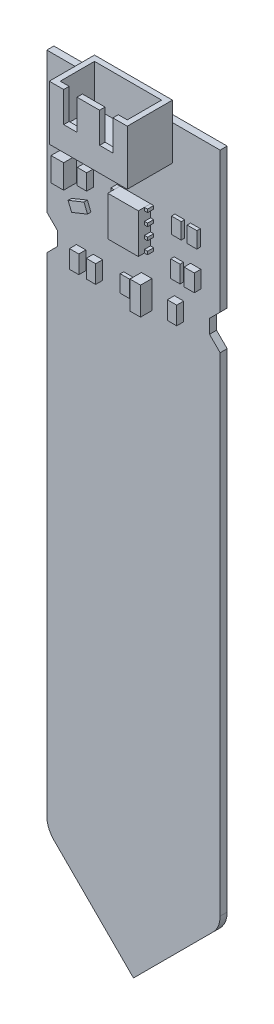
SolidWorks part; units mm, degrees
other "Camera1"
material "Plain Carbon Steel"
ref_plane "Front" through (0, 0, 0) normal (0, 0, 1) x (1, 0, 0)
ref_plane "Top" through (0, 0, 0) normal (0, 1, 0) x (1, 0, 0)
ref_plane "Right" through (0, 0, 0) normal (1, 0, 0) x (0, 0, -1)
ref_axis "X-Axis" through (0, 0, 0) along (1, 0, 0)
ref_axis "Y-Axis" through (0, 0, 0) along (0, 1, 0)
ref_axis "Z-Axis" through (0, 0, 0) along (0, 0, 1)
sketch "Sketch1" plane through (0, 0, 0) normal (0, 0, 1) x (1, 0, 0)
  line L0 (-11.1125, 0) -> (11.1125, 0)
  line L1 (11.1125, 0) -> (11.1125, -18)
  line L2 (-11.1125, 0) -> (-11.1125, -18)
  line L3 (-11.1125, -18) -> (-9.75, -19.3625)
  line L4 (-9.75, -19.3625) -> (-9.75, -21.1375)
  line L5 (-9.75, -21.1375) -> (-11.1125, -22.5)
  line L6 (-11.1125, -22.5) -> (-11.1125, -85.0724)
  line L7 (-10.1826, -87.3174) -> (0, -97.5)
  line L8 (0, -97.5) -> (10.1826, -87.3174)
  line L9 (11.1125, -85.0724) -> (11.1125, -22.5)
  line L10 (11.1125, -22.5) -> (9.75, -21.1375)
  line L11 (9.75, -21.1375) -> (9.75, -19.3625)
  line L12 (9.75, -19.3625) -> (11.1125, -18)
  line L13 (0, 0) -> (0, -97.5) construction
  arc A0 (10.1826, -87.3174) -> (11.1125, -85.0724) centre (7.9375, -85.0724) ccw
  arc A1 (-11.1125, -85.0724) -> (-10.1826, -87.3174) centre (-7.9375, -85.0724) ccw
  point P19 (0, 0)
  point P20 (11.1125, -16.1419)
  point P21 (0, 0)
  dimension "D2" = 3.175
  dimension "D1" = 22.225
  dimension "D3" = 19.5
  dimension "D4" = 18
  dimension "D5" = 4.5
  dimension "D6" = 97.5
extrude "Boss-Extrude1" add sketch "Sketch1" along normal blind 0.9
sketch "Sketch2" plane through (0, 0, 0.9) normal (0, 0, 1) x (1, 0, 0)
  line L0 (11.1125, 0) -> (-11.1125, 0) construction
  line L1 (-7.3125, -22) -> (-6.1125, -22)
  line L2 (-7.3125, -22) -> (-7.3125, -19.7)
  line L3 (-7.3125, -19.7) -> (-6.1125, -19.7)
  line L4 (-6.1125, -22) -> (-6.1125, -19.7)
  line L5 (-5.1525, -22) -> (-3.9525, -22)
  line L6 (-5.1525, -22) -> (-5.1525, -19.7)
  line L7 (-5.1525, -19.7) -> (-3.9525, -19.7)
  line L8 (-3.9525, -22) -> (-3.9525, -19.7)
  line L9 (-11.1125, 0) -> (-11.1125, -18) construction
  line L10 (11.1125, -18) -> (11.1125, 0) construction
  line L11 (-1.2675, -21.86) -> (-0.0675, -21.86)
  line L12 (-1.2675, -21.86) -> (-1.2675, -19.7)
  line L13 (-1.2675, -19.7) -> (-0.0675, -19.7)
  line L14 (-0.0675, -21.86) -> (-0.0675, -19.7)
  line L15 (1.0125, -22.2) -> (2.3625, -22.2)
  line L16 (1.0125, -22.2) -> (1.0125, -18.64)
  line L17 (1.0125, -18.64) -> (2.3625, -18.64)
  line L18 (2.3625, -22.2) -> (2.3625, -18.64)
  line L19 (5.2425, -21.4) -> (6.4425, -21.4)
  line L20 (5.2425, -21.4) -> (5.2425, -19.1)
  line L21 (5.2425, -19.1) -> (6.4425, -19.1)
  line L22 (6.4425, -21.4) -> (6.4425, -19.1)
  line L23 (-7.4957, -16) -> (-5.4576, -15.1717)
  line L24 (-8.9225, -9.79) -> (-7.3125, -9.79)
  line L25 (-8.9225, -9.79) -> (-8.9225, -12.84)
  line L26 (-8.9225, -12.84) -> (-7.3125, -12.84)
  line L27 (-7.3125, -9.79) -> (-7.3125, -12.84)
  line L28 (-6.3125, -10.18) -> (-5.1125, -10.18)
  line L29 (-6.3125, -10.18) -> (-6.3125, -12.22)
  line L30 (-6.3125, -12.22) -> (-5.1125, -12.22)
  line L31 (-5.1125, -10.18) -> (-5.1125, -12.22)
  line L32 (-1.7225, -10.42) -> (2.1875, -10.42)
  line L33 (-1.7225, -10.42) -> (-1.7225, -15.5)
  line L34 (-1.7225, -15.5) -> (2.1875, -15.5)
  line L35 (2.1875, -10.42) -> (2.1875, -15.5)
  line L36 (5.3125, -10) -> (6.5625, -10)
  line L37 (5.3125, -10) -> (5.3125, -12.05)
  line L38 (5.3125, -12.05) -> (6.5625, -12.05)
  line L39 (6.5625, -10) -> (6.5625, -12.05)
  line L40 (7.3125, -10) -> (8.5625, -10)
  line L41 (7.3125, -10) -> (7.3125, -12.05)
  line L42 (7.3125, -12.05) -> (8.5625, -12.05)
  line L43 (8.5625, -10) -> (8.5625, -12.05)
  line L44 (5.2125, -14.8) -> (6.4125, -14.8)
  line L45 (5.2125, -14.8) -> (5.2125, -17)
  line L46 (5.2125, -17) -> (6.4125, -17)
  line L47 (6.4125, -14.8) -> (6.4125, -17)
  line L48 (7.3125, -14.47) -> (8.6325, -14.47)
  line L49 (7.3125, -14.47) -> (7.3125, -16.67)
  line L50 (7.3125, -16.67) -> (8.6325, -16.67)
  line L51 (8.6325, -14.47) -> (8.6325, -16.67)
  line L52 (-7.4957, -16) -> (-7.9475, -14.8883)
  line L53 (-5.4576, -15.1717) -> (-5.9094, -14.06)
  line L54 (-7.9475, -14.8883) -> (-5.9094, -14.06)
  dimension "D1" = 22
  dimension "D2" = 1.2
  dimension "D3" = 2.3
  dimension "D4" = 5
  dimension "D5" = 2.16
  dimension "D6" = 2.16
  dimension "D7" = 1.2
  dimension "D8" = 1.35
  dimension "D9" = 3.56
  dimension "D10" = 0.2
  dimension "D11" = 10.1
  dimension "D12" = 12.38
  dimension "D13" = 5.87
  dimension "D14" = 21.4
  dimension "D15" = 1.61
  dimension "D16" = 3.05
  dimension "D17" = 2.04
  dimension "D18" = 1.2
  dimension "D19" = 5.08
  dimension "D20" = 3.91
  dimension "D21" = 1.32
  dimension "D22" = 1.25
  dimension "D23" = 1.2
  dimension "D24" = 1.25
  dimension "D25" = 2.05
  dimension "D26" = 12.05
  dimension "D27" = 3.8
  dimension "D28" = 5.8
  dimension "D29" = 2.2
  dimension "D30" = 17
  dimension "D31" = 5.9
  dimension "D32" = 3.8
  dimension "D33" = 16.67
  dimension "D34" = 13.3
  dimension "D35" = 15.5
  dimension "D36" = 12.84
  dimension "D37" = 3.8
  dimension "D38" = 12.22
  dimension "D39" = 6
  dimension "D40" = 2.2
  dimension "D41" = 1.2
  dimension "D42" = 16
  dimension "D43" = 14.06
  dimension "D44" = 19.06
extrude "Boss-Extrude2" add sketch "Sketch2" along normal blind 1.57 separate body contours L32 L35 L34 L33
extrude "Boss-Extrude3" add sketch "Sketch2<3>" along normal blind 0.44 separate body contours L43 L40 L41 L42 | L39 L36 L37 L38 | L47 L44 L45 L46 | L54 L52 L23 L53 | L11 L14 L13 L12 region at (-0.6675, -20.78, 0.9) region at (-6.7025, -15.03, 0.9) region at (5.9375, -11.025, 0.9) region at (7.9375, -11.025, 0.9) region at (5.8125, -15.9, 0.9)
sketch "Sketch2<3>" plane through (0, 0, 0.9) normal (0, 0, 1) x (1, 0, 0) same geometry as "Sketch2"
extrude "Boss-Extrude4" add sketch "Sketch2<4>" along normal blind 1.65 separate body contours L27 L24 L25 L26 region at (-8.1175, -11.315, 0.9)
sketch "Sketch2<4>" plane through (0, 0, 0.9) normal (0, 0, 1) x (1, 0, 0) same geometry as "Sketch2"
extrude "Boss-Extrude5" add sketch "Sketch2<5>" along normal blind 0.9 separate body contours L1 L4 L3 L2 | L5 L8 L7 L6 | L31 L28 L29 L30 | L19 L22 L21 L20 region at (-6.7125, -20.85, 0.9) region at (-4.5525, -20.85, 0.9) region at (5.8425, -20.25, 0.9) region at (-5.7125, -11.2, 0.9)
sketch "Sketch2<5>" plane through (0, 0, 0.9) normal (0, 0, 1) x (1, 0, 0) same geometry as "Sketch2"
extrude "Boss-Extrude6" add sketch "Sketch2<6>" along normal blind 1.46 separate body contours L15 L18 L17 L16 region at (1.6875, -20.42, 0.9)
sketch "Sketch2<6>" plane through (0, 0, 0.9) normal (0, 0, 1) x (1, 0, 0) same geometry as "Sketch2"
extrude "Boss-Extrude7" add sketch "Sketch2<7>" along normal blind 0.83 separate body contours L51 L48 L49 L50 region at (7.9725, -15.57, 0.9)
sketch "Sketch2<7>" plane through (0, 0, 0.9) normal (0, 0, 1) x (1, 0, 0) same geometry as "Sketch2"
sketch "Sketch4" plane through (0, 0, 0.9) normal (0, 0, 1) x (1, 0, 0)
  line L0 (11.1125, 0) -> (-11.1125, 0) construction
  line L1 (-5, -4.5) -> (5, -4.5)
  line L2 (-5, -4.5) -> (-5, 2.5)
  line L3 (-5, 2.5) -> (5, 2.5)
  line L4 (5, -4.5) -> (5, 2.5)
  line L5 (0, 0) -> (0, 2.5) construction
  dimension "D1" = 10
  dimension "D2" = 7
  dimension "D3" = 2.5
extrude "Boss-Extrude8" add sketch "Sketch4" along normal blind 5.8 separate body
shell "Shell1" thickness 0.7 removed face at (0, 2.5, 3.8)
sketch "Sketch5" plane through (0, 0, 6.7) normal (0, 0, 1) x (1, 0, 0)
  line L0 (5, 2.5) -> (-5, 2.5) construction
  line L1 (-3.15, 2.5) -> (-1.45, 2.5)
  line L2 (-3.15, 2.5) -> (-3.15, -1.4)
  line L3 (-3.15, -1.4) -> (-1.45, -1.4)
  line L4 (-1.45, 2.5) -> (-1.45, -1.4)
  line L5 (-1.45, -1.4) -> (1.45, -1.4) construction
  line L6 (1.45, 2.5) -> (3.15, 2.5)
  line L7 (1.45, 2.5) -> (1.45, -1.4)
  line L8 (1.45, -1.4) -> (3.15, -1.4)
  line L9 (3.15, 2.5) -> (3.15, -1.4)
  line L10 (0, 0) -> (0, -1.4) construction
  line L11 (5, -4.5) -> (5, 2.5) construction
  dimension "D1" = 2.9
  dimension "D2" = 1.85
  dimension "D3" = 3.9
extrude "Cut-Extrude1" cut sketch "Sketch5" against normal up to next (0.7 mm away)
sketch "Sketch6" plane through (0, 0, 0) normal (0, 0, -1) x (-1, 0, 0)
  line L0 (-2.19, -4.5) -> (-0.35, -4.5) construction
  line L1 (-2.89, -4.15) -> (-2.19, -4.15)
  line L2 (-2.89, -4.15) -> (-2.89, -4.85)
  line L3 (-2.89, -4.85) -> (-2.19, -4.85)
  line L4 (-2.19, -4.15) -> (-2.19, -4.85)
  line L5 (-0.35, -4.15) -> (0.35, -4.15)
  line L6 (-0.35, -4.15) -> (-0.35, -4.85)
  line L7 (-0.35, -4.85) -> (0.35, -4.85)
  line L8 (0.35, -4.15) -> (0.35, -4.85)
  line L9 (2.19, -4.15) -> (2.89, -4.15)
  line L10 (2.19, -4.15) -> (2.19, -4.85)
  line L11 (2.19, -4.85) -> (2.89, -4.85)
  line L12 (2.89, -4.15) -> (2.89, -4.85)
  line L13 (0.35, -4.5) -> (2.19, -4.5) construction
  line L14 (0, -4.15) -> (0, 0) construction
  line L15 (-11.1125, 0) -> (11.1125, 0) construction
  dimension "D1" = 0.7
  dimension "D2" = 2.54
  dimension "D3" = 4.5
extrude "Boss-Extrude9" add sketch "Sketch6" along normal blind 2.5 separate body
ref_plane "Plane1" through (0, 0, 1.685) normal (0, 0, -1) x (-1, 0, 0)
sketch "Sketch7" plane through (0, 0, 1.685) normal (0, 0, -1) x (-1, 0, 0)
  line L0 (-2.1875, -10.42) -> (-2.1875, -15.5) construction
  line L1 (-2.1875, -15.5) -> (-2.5875, -15.5)
  line L2 (-2.1875, -15.5) -> (-2.1875, -15.1)
  line L3 (-2.1875, -15.1) -> (-2.5875, -15.1)
  line L4 (-2.5875, -15.5) -> (-2.5875, -15.1)
  line L5 (-2.1875, -13.94) -> (-2.5875, -13.94)
  line L6 (-2.1875, -13.94) -> (-2.1875, -13.54)
  line L7 (-2.1875, -13.54) -> (-2.5875, -13.54)
  line L8 (-2.5875, -13.94) -> (-2.5875, -13.54)
  line L9 (-2.1875, -10.82) -> (-2.1875, -11.98) construction
  line L10 (-2.1875, -12.38) -> (-2.5875, -12.38)
  line L11 (-2.1875, -12.38) -> (-2.1875, -11.98)
  line L12 (-2.1875, -11.98) -> (-2.5875, -11.98)
  line L13 (-2.5875, -12.38) -> (-2.5875, -11.98)
  line L14 (-2.1875, -10.42) -> (-2.5875, -10.42)
  line L15 (-2.1875, -10.42) -> (-2.1875, -10.82)
  line L16 (-2.1875, -10.82) -> (-2.5875, -10.82)
  line L17 (-2.5875, -10.42) -> (-2.5875, -10.82)
  line L18 (-2.1875, -12.38) -> (-2.1875, -13.54) construction
  line L19 (-2.1875, -13.94) -> (-2.1875, -15.1) construction
  dimension "D1" = 0.4
extrude "Boss-Extrude10" add sketch "Sketch7" along normal up to surface (0.785 mm away) separate body up to face at (0.2325, -12.96, 0.9)
ref_plane "Plane2" through (0.2325, 0, 0) normal (1, 0, 0) x (0, 0, -1)
mirror "Mirror1" about plane through (0.2325, 0, 0) normal (1, 0, 0) of bodies 120 121 122 123
